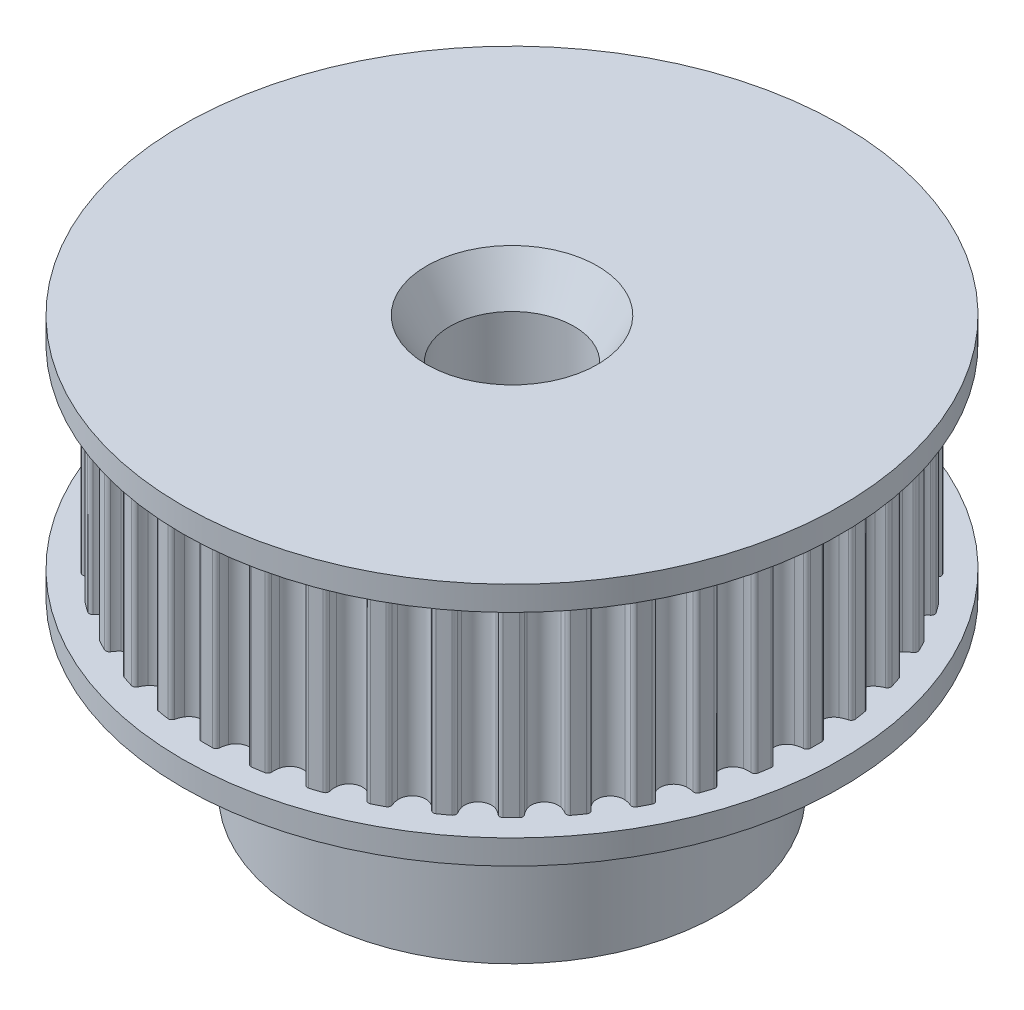
SolidWorks part; units mm, degrees
ref_plane "Front Plane" through (0, 0, 0) normal (0, 0, 1) x (1, 0, 0)
ref_plane "Top Plane" through (0, 0, 0) normal (0, 1, 0) x (1, 0, 0)
ref_plane "Right Plane" through (0, 0, 0) normal (1, 0, 0) x (0, 0, -1)
sketch "Sketch1" plane through (0, 0, 0) normal (0, 1, 0) x (1, 0, 0)
  circle A0 centre (0, 0) radius 13.5
  dimension "D1" = 27
extrude "Boss-Extrude1" add sketch "Sketch1" along normal blind 10
sketch "Sketch6" plane through (0, 0, 0) normal (0, 1, 0) x (1, 0, 0)
  circle A0 centre (0, 0) radius 8.5
  dimension "D2" = 17
extrude "Boss-Extrude2" add sketch "Sketch6" against normal blind 7
sketch "Sketch4" plane through (0, 0, 0) normal (0, 1, 0) x (1, 0, 0)
  circle A1 centre (0, 0) radius 2.54
  dimension "D1" = 5.08
extrude "Cut-Extrude3" cut sketch "Sketch4" along normal through all and the other way through all
ref_plane "Plane1" through (0, 1, 0) normal (0, 1, 0) x (1, 0, 0)
sketch "Sketch2" plane through (0, 1, 0) normal (0, 1, 0) x (1, 0, 0)
  line L0 (0, 0) -> (0, 15.3126) construction
  line L1 (-0.0014, -0.018) -> (0.9816, 12.2246) construction
  line L2 (0, 0) -> (1.407, 12.4893) construction
  line L3 (0, 0) -> (1.1174, 13.9156) construction
  line L4 (0, 12.48) -> (0, 13.8263)
  line L6 (1.9915, 12.3201) -> (2.2063, 13.6491)
  circle A0 centre (0, 0) radius 12.48 construction
  arc A1 (0, 12.48) -> (0.2536, 12.4774) centre (0, 0) cw
  arc A2 (0.2536, 12.4774) -> (0.4002, 12.3379) centre (0.2506, 12.3275) cw
  arc A3 (0.4002, 12.3379) -> (0.4664, 12.0434) centre (1.3978, 12.4077) ccw
  arc A4 (0.4664, 12.0434) -> (1.4613, 11.9635) centre (0.9833, 12.2456) ccw
  circle A5 centre (0, 0) radius 11.73 construction
  circle A6 centre (0, 0) radius 13.11 construction
  arc A7 (1.5737, 12.2437) -> (1.4613, 11.9635) centre (0.6001, 12.4717) cw
  arc A8 (1.7407, 12.358) -> (1.5737, 12.2437) centre (1.7198, 12.2095) ccw
  arc A9 (1.9915, 12.3201) -> (1.7407, 12.358) centre (0, 0) ccw
  arc A10 (0, 13.8263) -> (2.2063, 13.6491) centre (0, 0) cw
  point P16 (0.9989, 12.44)
  point P17 (1.3971, 12.4016)
  point P18 (0.9989, 12.44)
  dimension "D1" = 24.96
  dimension "D2" = 0.15
  dimension "D3" = 1
  dimension "D4" = 0.555
  dimension "D7" = 0.75
  dimension "D8" = 1.38
  dimension "D5" = 0.4
  dimension "D6" = 1
extrude "Cut-Extrude1" cut sketch "Sketch2" along normal blind 8
ref_axis "Axis2" through (0, 10, 0) along (0, -1, 0)
pattern_circular "CirPattern1" count 40 over 360 about axis through (0, 10, 0) along (0, -1, 0) of "Cut-Extrude1"
sketch "Sketch5" plane through (0, 0, 0) normal (0, 0, 1) x (1, 0, 0)
  line L0 (-3.5, 10) -> (0, 10)
  line L1 (13.5, 10) -> (-13.5, 10) construction
  line L5 (-3.5, -7) -> (0, -7)
  line L7 (-3.5, -7) -> (-0.6285, -4.1285)
  line L8 (0, 10) -> (0, 6.1244)
  line L9 (-8.5, -7) -> (8.5, -7) construction
  line L10 (-0.6285, -4.1285) -> (0, -4.1285)
  line L11 (-1.2624, 6.1244) -> (0, 6.1244)
  line L12 (-1.2624, 6.1244) -> (-3.5, 10)
  line L13 (0, -4.1285) -> (0, -7)
  point P8 (0, 0)
  point P11 (0, 0)
  point P13 (0, 0)
  dimension "D1" = 3.5
  dimension "D3" = 3.5
  dimension "D4" = 45
revolve "Cut-Revolve1" cut sketch "Sketch5" angle 360 about axis through (0, 10, 0) along (0, -1, 0)
sketch "Sketch7" plane through (0, 0, 0) normal (0, 0, 1) x (1, 0, 0)
  line L0 (-13.5805, -3.5) -> (12.2971, -3.5) construction
  line L1 (-8.5, 0) -> (8.5, 0) construction
  line L2 (-8.5, -7) -> (8.5, -7) construction
  line L3 (0, 0) -> (0, -10.6921) construction
  circle A0 centre (0, -3.5) radius 1.25
  dimension "D1" = 2.5
extrude "Cut-Extrude4" cut sketch "Sketch7" against normal through all
sketch "Sketch8" plane through (0, 0, 0) normal (1, 0, 0) x (0, 0, -1)
  line L0 (-10.2203, -3.5) -> (10.2203, -3.5) construction
  line L1 (-8.5, 0) -> (8.5, 0) construction
  line L2 (-8.5, -7) -> (8.5, -7) construction
  line L3 (0, 0) -> (0, -10.0387) construction
  line L4 (0, 10) -> (0, 0) construction
  circle A0 centre (0, -3.5) radius 1.25
  dimension "D1" = 2.5
extrude "Cut-Extrude5" cut sketch "Sketch8" against normal through all
